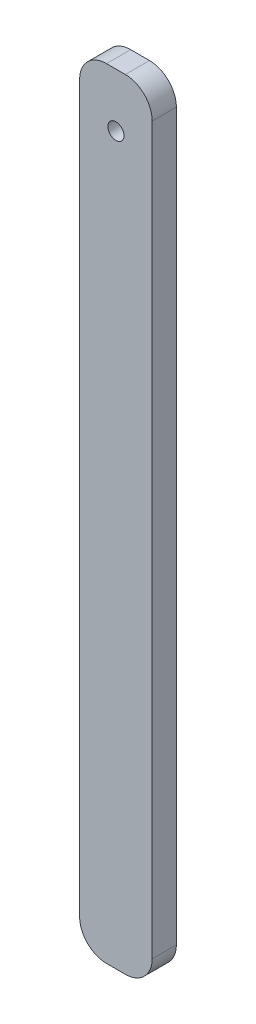
SolidWorks part; units mm, degrees
material "Beech"
ref_plane "Front" through (0, 0, 0) normal (0, 0, 1) x (1, 0, 0)
ref_plane "Top" through (0, 0, 0) normal (0, 1, 0) x (1, 0, 0)
ref_plane "Right" through (0, 0, 0) normal (1, 0, 0) x (0, 0, -1)
sketch "Sketch1" plane through (0, 0, 0) normal (0, 0, 1) x (1, 0, 0)
  line L1 (-3.5, -145) -> (3.5, -145)
  line L2 (-13.5, -135) -> (-13.5, 135)
  line L3 (-3.5, 145) -> (3.5, 145)
  line L4 (13.5, -135) -> (13.5, 135)
  line L5 (-13.5, -145) -> (13.5, 145) construction
  line L6 (-13.5, 145) -> (13.5, -145) construction
  circle A0 centre (0, 125) radius 3
  arc A1 (-3.5, -145) -> (-13.5, -135) centre (-3.5, -135) cw
  arc A2 (3.5, -145) -> (13.5, -135) centre (3.5, -135) ccw
  arc A3 (-13.5, 135) -> (-3.5, 145) centre (-3.5, 135) cw
  arc A4 (3.5, 145) -> (13.5, 135) centre (3.5, 135) cw
  point P0 (0, 0)
  dimension "D1" = 6
  dimension "D5" = 10
  dimension "D2" = 27
  dimension "D3" = 290
  dimension "D4" = 20
extrude "Boss-Extrude1" add sketch "Sketch1" along normal blind 9 contours A4 L3 A3 L2 A1 L1 A2 L4 A0 region at (0, -0.4581, 0)
